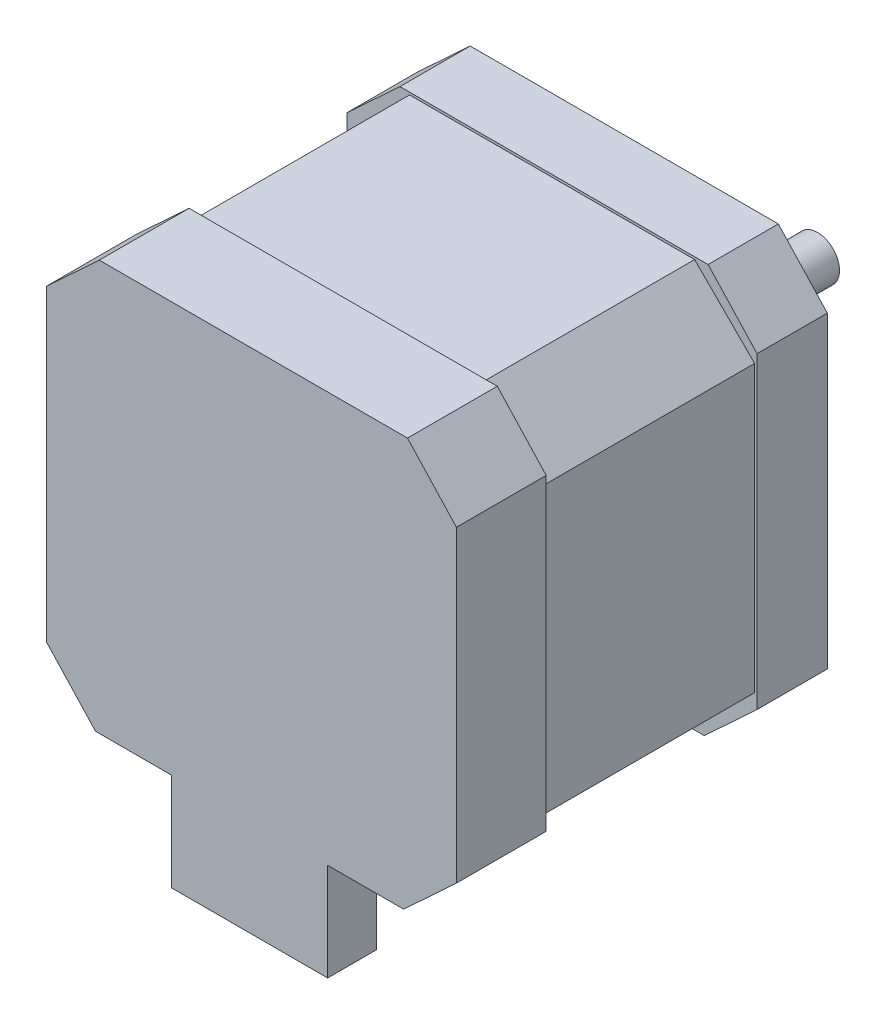
SolidWorks part; units mm, degrees
material "Ferro dúctil"
ref_plane "Plano frontal" through (0, 0, 0) normal (0, 0, 1) x (1, 0, 0)
ref_plane "Plano superior" through (0, 0, 0) normal (0, 1, 0) x (1, 0, 0)
ref_plane "Plano direito" through (0, 0, 0) normal (1, 0, 0) x (0, 0, -1)
sketch "Esboço1" plane through (0, 0, 0) normal (0, 0, 1) x (1, 0, 0)
  line L0 (-1.3818, -36.7436) -> (-36.7436, 1.3818)
  line L1 (-21, 21) -> (21, 21)
  line L2 (-21, 21) -> (-21, -21)
  line L3 (-21, -21) -> (21, -21)
  line L4 (21, 21) -> (21, -21)
  line L5 (-21, 21) -> (21, -21) construction
  line L6 (-21, -21) -> (21, 21) construction
  line L7 (-1.3818, -36.7436) -> (36.7436, -1.3818)
  line L8 (-36.7436, 1.3818) -> (1.3818, 36.7436)
  line L9 (36.7436, -1.3818) -> (1.3818, 36.7436)
  line L10 (-1.3818, -36.7436) -> (1.3818, 36.7436) construction
  line L11 (-36.7436, 1.3818) -> (36.7436, -1.3818) construction
  point P0 (0, 0)
  point P7 (0, 0)
  dimension "D1" = 42
  dimension "D2" = 52
extrude "Ressalto-extrusão1" add sketch "Esboço1" along normal blind 38 contours L4 L9 L1 L8 L2 L0 L3 L7 region at (0, 0, 0)
sketch "Esboço2" plane through (0, 0, 38) normal (0, 0, 1) x (1, 0, 0)
  line L1 (-20.75, -20.75) -> (20.75, -20.75)
  line L2 (-20.75, -20.75) -> (-20.75, 20.75)
  line L3 (-20.75, 20.75) -> (20.75, 20.75)
  line L4 (20.75, -20.75) -> (20.75, 20.75)
  line L5 (-20.75, -20.75) -> (20.75, 20.75) construction
  line L6 (-20.75, 20.75) -> (20.75, -20.75) construction
  line L7 (0, -35.3553) -> (-35.3553, 0)
  line L8 (0, -35.3553) -> (35.3553, 0)
  line L9 (-35.3553, 0) -> (0, 35.3553)
  line L10 (35.3553, 0) -> (0, 35.3553)
  line L11 (0, -35.3553) -> (0, 35.3553) construction
  line L12 (-35.3553, 0) -> (35.3553, 0) construction
  point P0 (0, 0)
  point P8 (-17.6777, 17.6777)
  point P9 (0, 0)
  dimension "D1" = 50
  dimension "D2" = 41.5
extrude "Corte-Extrusão-Fina1" cut sketch "Esboço2" against normal offset from surface (21.6 mm away) 7.2 from offset 9.2 thin contours L4 L10 L3 L9 L2 L7 L1 L8 up to face at (0, 0, 0) offset against normal yes thin type one direction wall 10
sketch "Esboço3" plane through (0, 0, 0) normal (0, 0, -1) x (-1, 0, 0)
  circle A0 centre (0, 0) radius 2.25
  dimension "D1" = 4.5
extrude "Ressalto-extrusão2" add sketch "Esboço3" along normal blind 20
sketch "Esboço4" plane through (0, 0, 0) normal (0, 0, -1) x (-1, 0, 0)
  circle A0 centre (0, 0) radius 10
  dimension "D1" = 20
extrude "Ressalto-extrusão3" add sketch "Esboço4" along normal blind 2
sketch "Esboço5" plane through (0, 0, 0) normal (0, 0, -1) x (-1, 0, 0)
  line L1 (15.5, 15.5) -> (-15.5, 15.5) construction
  line L2 (15.5, 15.5) -> (15.5, -15.5) construction
  line L3 (15.5, -15.5) -> (-15.5, -15.5) construction
  line L4 (-15.5, 15.5) -> (-15.5, -15.5) construction
  line L5 (15.5, 15.5) -> (-15.5, -15.5) construction
  line L6 (15.5, -15.5) -> (-15.5, 15.5) construction
  circle A0 centre (15.5, -15.5) radius 1.5
  circle A1 centre (-15.5, -15.5) radius 1.5
  circle A2 centre (-15.5, 15.5) radius 1.5
  circle A3 centre (15.5, 15.5) radius 1.5
  point P0 (0, 0)
  dimension "D1" = 3
  dimension "D2" = 31
extrude "Corte-extrusão1" cut sketch "Esboço5" against normal blind 10
sketch "Esboço7" plane through (0, -21, 0) normal (0, -1, 0) x (1, 0, 0)
  line L0 (-15.9842, 38) -> (15.5922, 38) construction
  line L1 (7.804, 33) -> (-8.196, 33)
  line L2 (7.804, 33) -> (7.804, 38)
  line L3 (7.804, 38) -> (-8.196, 38)
  line L4 (-8.196, 33) -> (-8.196, 38)
  line L5 (7.804, 33) -> (-8.196, 38) construction
  line L6 (7.804, 38) -> (-8.196, 33) construction
  line L7 (-15.9842, 0) -> (15.5922, 0) construction
  point P0 (-0.196, 35.5)
  point P10 (-0.196, 0)
  dimension "D1" = 5
  dimension "D2" = 16
extrude "Ressalto-extrusão4" add sketch "Esboço7" along normal blind 10
